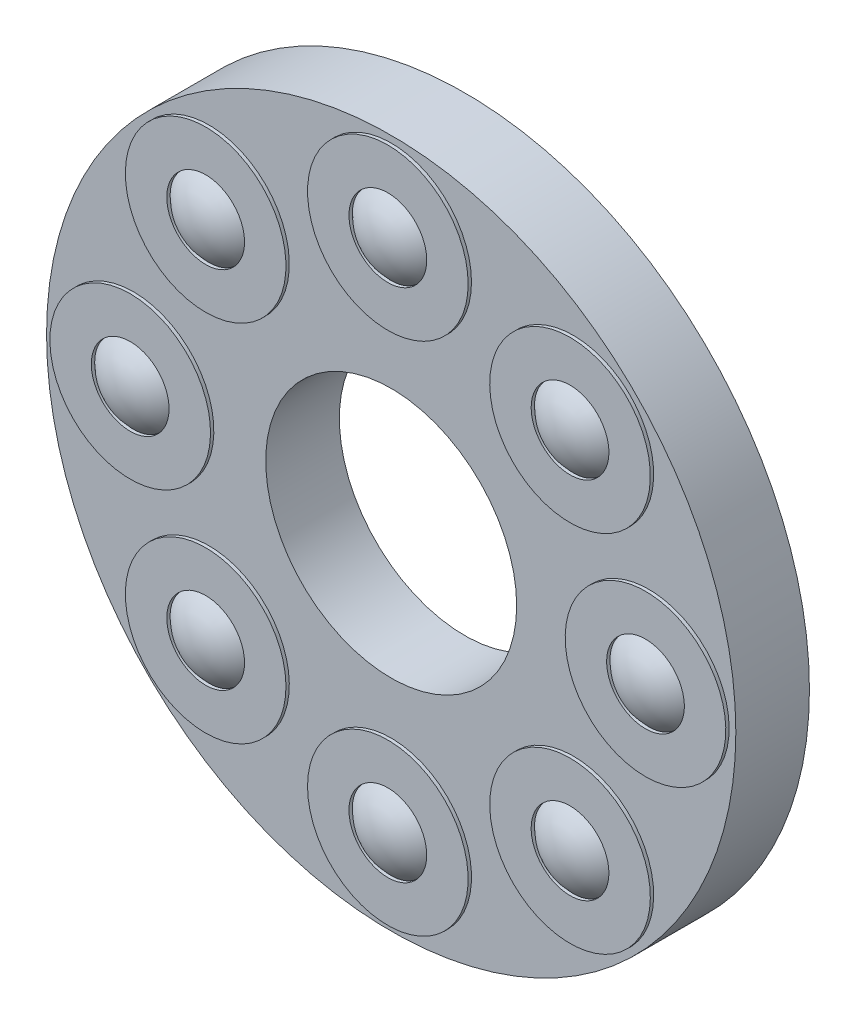
SolidWorks part; units mm, degrees
ref_plane "Front Plane" through (0, 0, 0) normal (0, 0, 1) x (1, 0, 0)
ref_plane "Top Plane" through (0, 0, 0) normal (0, 1, 0) x (1, 0, 0)
ref_plane "Right Plane" through (0, 0, 0) normal (1, 0, 0) x (0, 0, -1)
sketch "Sketch1" plane through (0, 0, 0) normal (0, 0, 1) x (1, 0, 0)
  line L0 (0, 0) -> (0, 12.4456) construction
  circle A0 centre (0, 0) radius 10.3
  circle A1 centre (0, 0) radius 3.75
  dimension "D1" = 20.6
  dimension "D2" = 7.5
extrude "Boss-Extrude1" add sketch "Sketch1" along normal blind 1.1 and the other way blind 1.1
sketch "Sketch2" plane through (0, 0, 0) normal (0, 0, 1) x (1, 0, 0)
  line L0 (0, 9.3) -> (0, 6.1)
  arc A0 (0, 6.1) -> (0, 9.3) centre (0, 7.7) ccw
  dimension "D2" = 3.2
  dimension "D1" = 7.7
ref_axis "Axis1" through (0, 7.7, 0) along (0, 1, 0)
revolve "Cut-Revolve4" cut sketch "Sketch2" angle 360 about axis through (0, 7.7, 0) along (0, 1, 0)
ref_axis "Axis2" through (0, 0, -1.1) along (0, 0, 1)
pattern_circular "CirPattern1" count 8 over 360 about axis through (0, 0, -1.1) along (0, 0, 1) of "Cut-Revolve4"
sketch "Sketch3" plane through (0, 0, 1.1) normal (0, 0, 1) x (1, 0, 0)
  line L0 (0, 7.7) -> (0, 15.2203) construction
  circle A0 centre (0, 7.7) radius 2.4
  circle A1 centre (0, 7.7) radius 1.1619
  dimension "D1" = 4.8
extrude "Boss-Extrude2" add sketch "Sketch3" along normal blind 0.1
pattern_circular "CirPattern2" count 8 over 360 about axis through (0, 0, -1.1) along (0, 0, 1) of "Boss-Extrude2"
sketch "Sketch4" plane through (0, 0, -1.1) normal (0, 0, -1) x (-1, 0, 0)
  line L0 (0, 0) -> (-4.43, 10.6949) construction
  line L2 (0, 7.7) -> (0, 15.2203) construction
  circle A0 centre (-2.143, 5.1737) radius 0.5
  dimension "D2" = 1
  dimension "D1" = 22.5
  dimension "D3" = 5.6
extrude "Boss-Extrude3" add sketch "Sketch4" along normal blind 0.1 draft 60
fillet "Fillet1" radius 0.5 1 edges at (1.8162, 5.1737, -1.2)
pattern_circular "CirPattern3" count 8 over 360 about axis through (0, 0, -1.1) along (0, 0, 1) of "Fillet1", "Boss-Extrude3"
sketch "Sketch5" plane through (0, 0, 0) normal (0, 0, 1) x (1, 0, 0)
  line L0 (0, 9.3) -> (0, 6.1)
  arc A0 (0, 6.1) -> (0, 9.3) centre (0, 7.7) ccw
  dimension "D1" = 3.2
revolve "Revolve1" add sketch "Sketch5" angle 360 about axis through (0, 7.7, 0) along (0, 1, 0)
pattern_circular "CirPattern4" count 8 over 360 about axis through (0, 0, -1.1) along (0, 0, 1) of "Revolve1"
